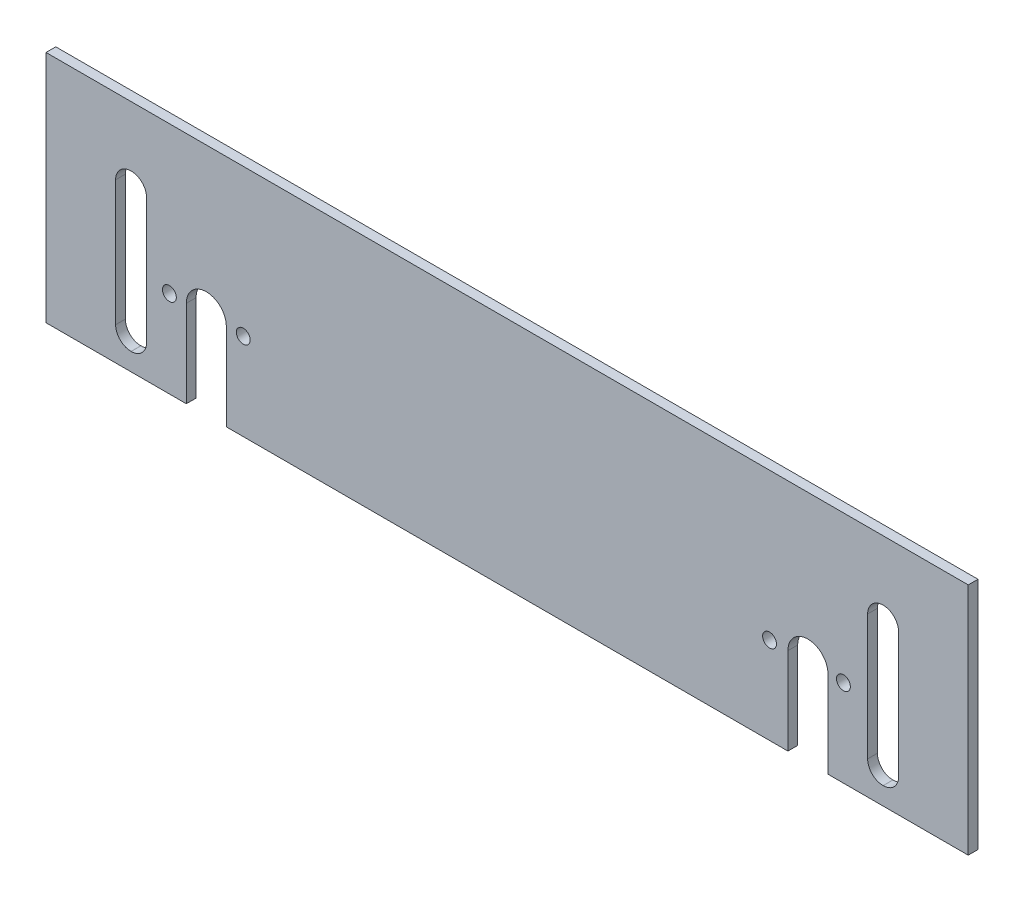
SolidWorks part; units mm, degrees
material "ABS"
ref_plane "X-Y Datum" through (0, 0, 0) normal (0, 0, 1) x (1, 0, 0)
ref_plane "X-Z Datum" through (0, 0, 0) normal (0, 1, 0) x (1, 0, 0)
ref_plane "Y-Z Datum" through (0, 0, 0) normal (1, 0, 0) x (0, 0, -1)
sketch "Sketch1" plane through (0, 0, 0) normal (0, 0, 1) x (1, 0, 0)
  line L1 (-149.85, 38.0375) -> (149.85, 38.0375)
  line L2 (-149.85, 38.0375) -> (-149.85, -38.0375)
  line L3 (-149.85, -38.0375) -> (149.85, -38.0375)
  line L4 (149.85, 38.0375) -> (149.85, -38.0375)
  line L5 (-149.85, 38.0375) -> (149.85, -38.0375) construction
  line L6 (-149.85, -38.0375) -> (149.85, 38.0375) construction
  point P0 (0, 0)
  dimension "D1" = 76.075
  dimension "D2" = 299.7
extrude "Boss-Extrude1" add sketch "Sketch1" along normal blind 3.175
sketch "Sketch3" plane through (0, 0, 0) normal (0, 0, -1) x (-1, 0, 0)
  line L0 (104.25, -9.7625) -> (104.25, -38.0375)
  line L1 (149.85, -38.0375) -> (-149.85, -38.0375) construction
  line L2 (91.25, -9.7625) -> (91.25, -38.0375)
  line L3 (149.85, -38.0375) -> (-149.85, -38.0375)
  line L4 (-104.25, -9.7625) -> (-104.25, -38.0375)
  line L5 (-91.25, -9.7625) -> (-91.25, -38.0375)
  circle A0 centre (97.75, -9.7625) radius 5.75 construction
  circle A1 centre (-97.75, -9.7625) radius 5.75 construction
  circle A2 centre (97.75, -9.7625) radius 5.75 construction
  circle A3 centre (-97.75, -9.7625) radius 5.75 construction
  circle A4 centre (97.75, -9.7625) radius 6.5
  circle A5 centre (-97.75, -9.7625) radius 6.5
  line M2 (-149.85, -38.0375) -> (149.85, -38.0375)
  dimension "D1" = 13
extrude "Cut-Extrude1" cut sketch "Sketch3" against normal through all contours A5 A3 | A3 | A5 L4 L3 L5 | A2 | A4 A2 | A4 L2 L0 M2 region at (97.75, -26.4071, 0) region at (-97.75, -9.7625, 0) region at (-97.75, -26.4071, 0) region at (97.75, -9.7625, 0)
sketch "Sketch4" plane through (0, 0, 0) normal (0, 0, -1) x (-1, 0, 0)
  circle A0 centre (-109.288, -9.7625) radius 2 construction
  circle A1 centre (-85.288, -9.7625) radius 2 construction
  circle A2 centre (85.75, -9.7625) radius 2 construction
  circle A3 centre (109.75, -9.7625) radius 2 construction
  circle A4 centre (-109.288, -9.7625) radius 2 construction
  circle A5 centre (-85.288, -9.7625) radius 2 construction
  circle A6 centre (85.75, -9.7625) radius 2 construction
  circle A7 centre (109.75, -9.7625) radius 2 construction
hole_wizard "M4 Clearance Hole1" positions "Sketch5" profile "Sketch6" hole size "M4" standard "ANSI Metric" end condition through all
sketch "Sketch5" plane through (0, 0, 0) normal (0, 0, -1) x (-1, 0, 0)
  point P0 (-109.288, -9.7625)
  point P3 (-85.288, -9.7625)
  point P6 (85.75, -9.7625)
  point P9 (109.75, -9.7625)
sketch "Sketch6" plane through (109.288, -9.7625, 0) normal (1, 0, 0) x (0, 1, 0)
  line L0 (0, 0) -> (0, 3.175)
  line L1 (0, 3.175) -> (2.25, 3.175)
  line L2 (2.25, 3.175) -> (2.25, 0)
  line L5 (2.25, 0) -> (0, 0)
  line L11 (0, -6.35) -> (0, 107.95) construction
  dimension "Thru Hole Dia." = 4.5
  dimension "Thru Hole Depth" = 3.175
sketch "Sketch8" plane through (0, 0, 3.175) normal (0, 0, 1) x (1, 0, 0)
  line L1 (122.1609, 18.5125) -> (122.2247, 18.5125)
  line L4 (122.1928, -32.2824) -> (122.1928, 18.5125) construction
  line L5 (122.1609, -32.2824) -> (122.2247, -32.2824)
  line L6 (117.1609, -27.2824) -> (117.1609, 13.5125)
  line L8 (127.2247, -27.2824) -> (127.2247, 13.5125)
  line L9 (117.1609, -32.2824) -> (127.2247, 18.5125) construction
  line L10 (117.1609, 18.5125) -> (127.2247, -32.2824) construction
  arc A0 (122.1609, -32.2824) -> (117.1609, -27.2824) centre (122.1609, -27.2824) cw
  arc A1 (122.2247, -32.2824) -> (127.2247, -27.2824) centre (122.2247, -27.2824) ccw
  arc A2 (127.2247, 13.5125) -> (122.2247, 18.5125) centre (122.2247, 13.5125) ccw
  arc A3 (122.1609, 18.5125) -> (117.1609, 13.5125) centre (122.1609, 13.5125) ccw
  point P0 (122.1928, -6.885)
  dimension "D1" = 5
extrude "Cut-Extrude4" cut sketch "Sketch8" against normal through all
mirror "Mirror3" about plane through (0, 0, 0) normal (1, 0, 0) of "Cut-Extrude4"
